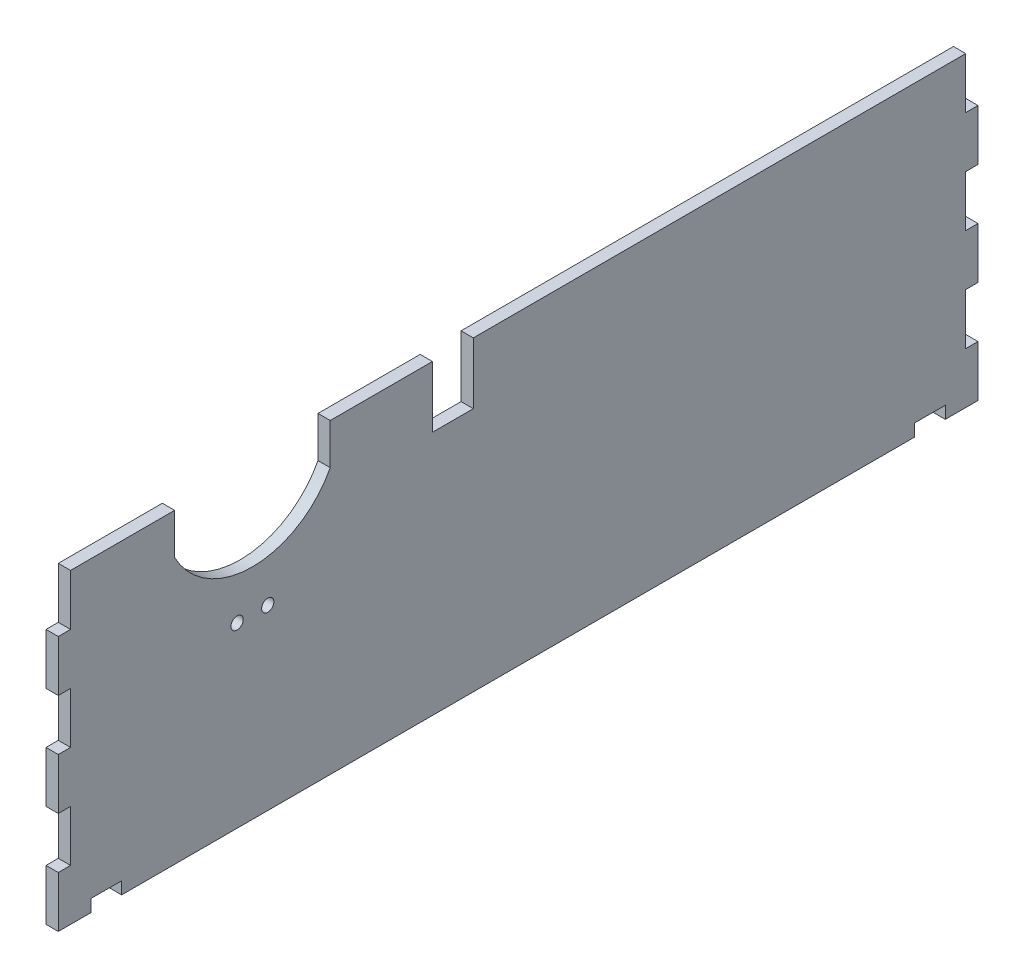
SolidWorks part; units mm, degrees
ref_plane "Front" through (0, 0, 0) normal (0, 0, 1) x (1, 0, 0)
ref_plane "Top" through (0, 0, 0) normal (0, 1, 0) x (1, 0, 0)
ref_plane "Right" through (0, 0, 0) normal (1, 0, 0) x (0, 0, -1)
sketch "Sketch1" plane through (0, 0, 0) normal (1, 0, 0) x (0, 0, -1)
  line L1 (0, 0) -> (-450, 0)
  line L2 (0, 0) -> (0, 150)
  line L3 (0, 150) -> (-450, 150)
  line L4 (-450, 0) -> (-450, 150)
  dimension "D1" = 450
  dimension "D2" = 150
extrude "Boss-Extrude1" add sketch "Sketch1" along normal blind 6
sketch "Sketch2" plane through (6, 0, 0) normal (1, 0, 0) x (0, 0, -1)
  line L0 (-450, 150) -> (-450, 0) construction
  line L1 (-450, 150) -> (-444, 150)
  line L2 (-450, 150) -> (-450, 125)
  line L3 (-450, 125) -> (-444, 125)
  line L4 (-444, 150) -> (-444, 125)
  line L5 (0, 150) -> (-450, 150) construction
  dimension "D1" = 6
  dimension "D2" = 25
extrude "Cut-Extrude1" cut sketch "Sketch2" against normal through all
pattern_linear "LPattern1" count 3 spacing 50 along (0, -1, 0) count 2 spacing 444 along (0, 0, -1) of "Cut-Extrude1"
sketch "Sketch3" plane through (6, 0, 0) normal (1, 0, 0) x (0, 0, -1)
  line L0 (-450, 0) -> (0, 0) construction
  line L1 (-434, 0) -> (-419, 0)
  line L2 (-434, 0) -> (-434, 6)
  line L3 (-434, 6) -> (-419, 6)
  line L4 (-419, 0) -> (-419, 6)
  line L6 (-444, 25) -> (-444, 50) construction
  dimension "D1" = 10
  dimension "D2" = 15
  dimension "D3" = 6
extrude "Cut-Extrude2" cut sketch "Sketch3" against normal through all
pattern_linear "LPattern2" count 2 spacing 403 along (0, 0, -1) of "Cut-Extrude2"
sketch "Sketch4" plane through (6, 0, 0) normal (1, 0, 0) x (0, 0, -1)
  line L0 (-393.0657, 130) -> (-316.9343, 130) construction
  line L1 (-355, 150) -> (-355, 107) construction
  line L2 (-450, 125) -> (-450, 100) construction
  line L3 (-393.0657, 130) -> (-393.0657, 150)
  line L4 (-6, 150) -> (-444, 150) construction
  line L5 (-393.0657, 150) -> (-316.9343, 150)
  line L6 (-316.9343, 150) -> (-316.9343, 130)
  arc A0 (-393.0657, 130) -> (-316.9343, 130) centre (-355, 150) ccw
  circle A1 centre (-362.5, 87) radius 3
  circle A3 centre (-347.5, 87) radius 3
  dimension "D4" = 63
  dimension "D1" = 43
  dimension "D6" = 6
  dimension "D2" = 20
  dimension "D3" = 95
  dimension "D5" = 7.5
extrude "Cut-Extrude3" cut sketch "Sketch4" against normal blind 10
sketch "Sketch5" plane through (6, 0, 0) normal (1, 0, 0) x (0, 0, -1)
  line L0 (-6, 150) -> (-316.9343, 150) construction
  line L1 (-266.9343, 150) -> (-246.9343, 150)
  line L2 (-266.9343, 150) -> (-266.9343, 120)
  line L3 (-266.9343, 120) -> (-246.9343, 120)
  line L4 (-246.9343, 150) -> (-246.9343, 120)
  line L5 (-316.9343, 130) -> (-316.9343, 150) construction
  dimension "D1" = 20
  dimension "D2" = 30
  dimension "D3" = 50
extrude "Cut-Extrude4" cut sketch "Sketch5" against normal blind 10
